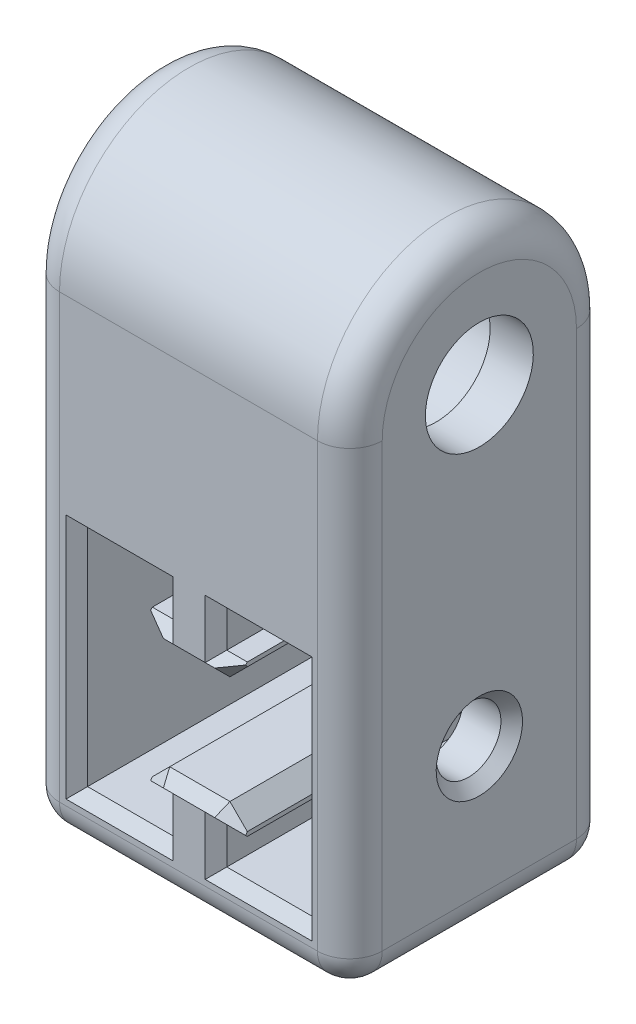
SolidWorks part; units mm, degrees
ref_plane "Front Plane" through (0, 0, 0) normal (0, 0, 1) x (1, 0, 0)
ref_plane "Top Plane" through (0, 0, 0) normal (0, 1, 0) x (1, 0, 0)
ref_plane "Right Plane" through (0, 0, 0) normal (1, 0, 0) x (0, 0, -1)
sketch "Sketch1" plane through (0, 0, 0) normal (0, 0, 1) x (1, 0, 0)
  line L0 (0, -15) -> (0, 15) construction
  line L1 (0, 15) -> (14.8993, 15)
  line L2 (14.8993, 15) -> (14.8993, -14.9496)
  line L3 (14.8993, -14.9496) -> (-15, -14.9496)
  line L4 (-15, -14.9496) -> (-15, 15)
  line L5 (-15, 15) -> (0, 15)
  line L6 (0, -10.4) -> (0, 10.4) construction
  line L7 (0, 10.4) -> (-10.4, 10.4) construction
  line L8 (-10.4, 10.4) -> (-2.5, 10.4)
  line L9 (-2.5, 10.4) -> (-2.5, 7)
  line L10 (-2.5, 7) -> (0, 7) construction
  line L11 (-2.5, 7) -> (-4.4, 7)
  line L12 (-4.4, 7) -> (-4.4, 6.61)
  line L13 (-4.4, 6.61) -> (-2.79, 5)
  line L14 (-2.79, 5) -> (0, 5) construction
  line L15 (-2.79, 5) -> (2.79, 5)
  line L16 (-10.4, 10.4) -> (0, 0) construction
  line L22 (-10.4, 10.4) -> (-10.4, 2.5)
  line L23 (0, 0) -> (-11.0308, 0) construction
  line L24 (4.4, 6.61) -> (2.79, 5)
  line L25 (4.4, 7) -> (4.4, 6.61)
  line L26 (2.5, 7) -> (4.4, 7)
  line L27 (2.5, 10.4) -> (2.5, 7)
  line L28 (10.4, 10.4) -> (2.5, 10.4)
  line L29 (10.4, 10.4) -> (10.4, 2.5)
  line L35 (-10.4, -10.4) -> (0, 0) construction
  line L36 (-2.79, -5) -> (0, -5) construction
  line L37 (-2.5, -7) -> (0, -7) construction
  line L38 (0, -10.4) -> (-10.4, -10.4) construction
  line L43 (10.4, -10.4) -> (10.4, -2.5)
  line L44 (10.4, -10.4) -> (2.5, -10.4)
  line L45 (2.5, -10.4) -> (2.5, -7)
  line L46 (2.5, -7) -> (4.4, -7)
  line L47 (4.4, -7) -> (4.4, -6.61)
  line L48 (4.4, -6.61) -> (2.79, -5)
  line L49 (-10.4, -10.4) -> (-10.4, -2.5)
  line L54 (-2.79, -5) -> (2.79, -5)
  line L55 (-4.4, -6.61) -> (-2.79, -5)
  line L56 (-4.4, -7) -> (-4.4, -6.61)
  line L57 (-2.5, -7) -> (-4.4, -7)
  line L58 (-2.5, -10.4) -> (-2.5, -7)
  line L59 (-10.4, -10.4) -> (-2.5, -10.4)
  line L60 (-10.4, 2.5) -> (-10.4, -2.5)
  line L61 (10.4, -2.5) -> (10.4, 2.5)
  point P43 (5, 0)
  point P58 (-5, 0)
  point P61 (-3.45, 7)
  dimension "D1" = 2.5
  dimension "D2" = 2.79
  dimension "D3" = 1.9
  dimension "D4" = 135
  dimension "D5" = 2
  dimension "D6" = 15
  dimension "D7" = 15
  dimension "D8" = 10.4
  dimension "D9" = 90
  dimension "D10" = 3.4
extrude "Boss-Extrude1" add sketch "Sketch1" along normal blind 24
sketch "Sketch5" plane through (-15, 0, 0) normal (-1, 0, 0) x (0, 0, 1)
  line L0 (0, 15) -> (0, 22.5)
  line L2 (0, 15) -> (24, 15)
  line L9 (24, 22.5) -> (24, 15)
  line L11 (12, 22.5) -> (12, 29) construction
  line L12 (0, 22.5) -> (0, 29)
  line L13 (24, 29) -> (24, 22.5)
  circle A2 centre (12, 29) radius 6.9
  arc A3 (0, 29) -> (24, 29) centre (12, 29) cw
  dimension "D3" = 13.8
  dimension "D1" = 7.5
  dimension "D2" = 24
extrude "Boss-Extrude3" add sketch "Sketch5" against normal through all
sketch "Sketch3" plane through (-15, 0, 0) normal (-1, 0, 0) x (0, 0, 1)
  line L0 (12, 0) -> (24, 7.0252) construction
  line L2 (0, 0) -> (12, 0) construction
  line L3 (24, 29) -> (24, -14.9496) construction
  circle A0 centre (12, 0) radius 3
extrude "Cut-Extrude1" cut sketch "Sketch3" against normal through all
sketch "Sketch6" plane through (14.8993, 0, 0) normal (1, 0, 0) x (0, 0, -1)
  line L0 (-12, 22.1) -> (-12, 29) construction
  circle A0 centre (-12, 29) radius 6.9 construction
  circle A1 centre (-12, 29) radius 5
  circle A2 centre (-12, 29) radius 12
extrude "Boss-Extrude4" add sketch "Sketch6" against normal blind 4
fillet "Fillet1" radius 3 10 edges at (-0.0504, -14.9496, 24) (14.8993, 7.0252, 24) (-15, 7.0252, 24) (14.8993, 7.0252, 0) (-15, 7.0252, 0) (-0.0504, -14.9496, 0) (14.8993, -14.9496, 12) (-15, -14.9496, 12) (14.8993, 41, 12) (-15, 41, 12)
chamfer "Chamfer1" distance 1 angle 45 43 edges at (-15, 0, 15) (-15, 29, 18.9) (14.8993, 0, 15) (-2.5, 8.7, 24) (-6.45, 10.4, 24) (-10.4, 0, 24) (-6.45, -10.4, 24) (-2.5, -8.7, 24) (-3.45, -7, 24) (-3.595, -5.805, 24) (0, -5, 24) (3.595, -5.805, 24) (3.45, -7, 24) (2.5, -8.7, 24) (6.45, -10.4, 24) (10.4, 0, 24) (6.45, 10.4, 24) (2.5, 8.7, 24) (3.45, 7, 24) (3.595, 5.805, 24) (0, 5, 24) (-3.595, 5.805, 24) (-3.45, 7, 24) (-3.595, 5.805, 0) (0, 5, 0) (3.595, 5.805, 0) (3.45, 7, 0) (2.5, 8.7, 0) (6.45, 10.4, 0) (10.4, 0, 0) (6.45, -10.4, 0) (2.5, -8.7, 0) (3.45, -7, 0) (3.595, -5.805, 0) (0, -5, 0) (-3.595, -5.805, 0) (-3.45, -7, 0) (-2.5, -8.7, 0) (-6.45, -10.4, 0) (-10.4, 0, 0) (-6.45, 10.4, 0) (-2.5, 8.7, 0) (-3.45, 7, 0)
